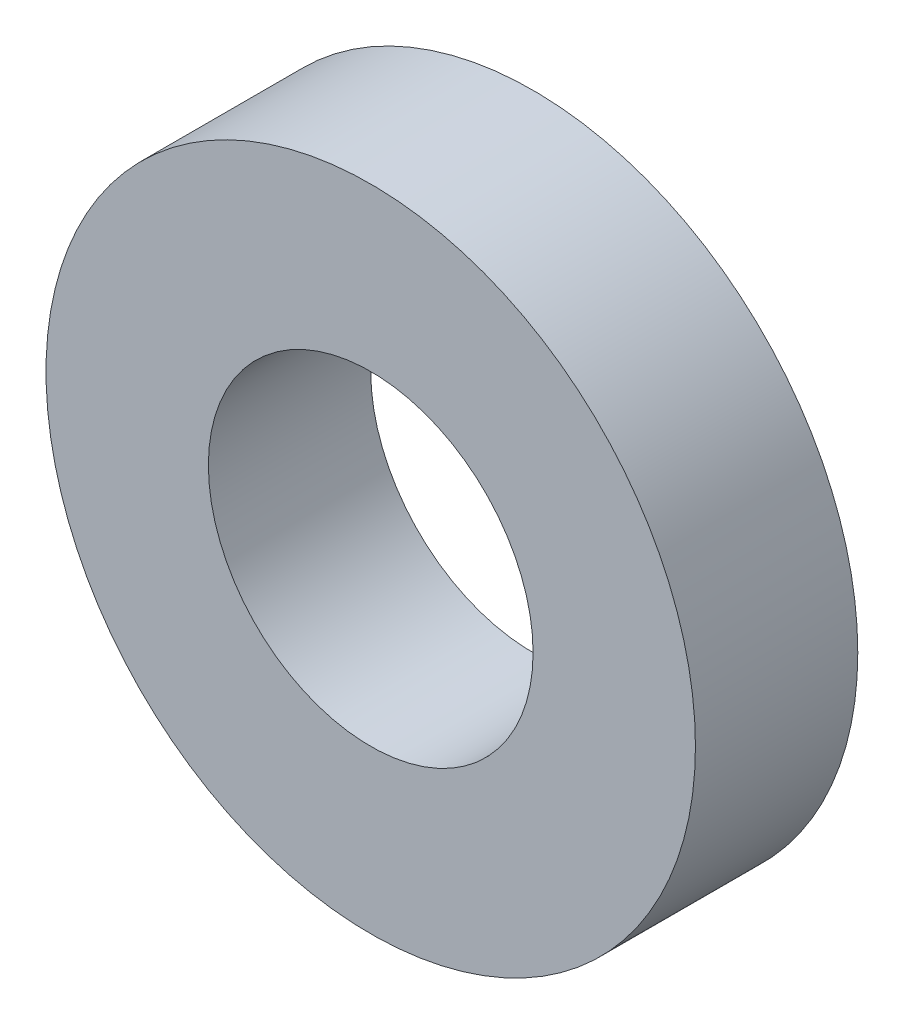
SolidWorks part; units mm, degrees
material "AISI 321 Annealed Stainless Steel (SS)"
ref_plane "Front (1)" through (0, 0, 0) normal (0, 0, 1) x (1, 0, 0)
ref_plane "Top (2)" through (0, 0, 0) normal (0, 1, 0) x (1, 0, 0)
ref_plane "Right (3)" through (0, 0, 0) normal (1, 0, 0) x (0, 0, -1)
ref_axis "X Axis" through (13.5064, 0, 0) along (-1, 0, 0)
ref_axis "Y Axis" through (0, 12.3593, 0) along (0, -1, 0)
ref_axis "Z Axis" through (0, 0, 14.1119) along (0, 0, -1)
sketch "Sketch2" plane through (0, 0, 0) normal (0, 0, 1) x (1, 0, 0)
  circle A0 centre (0, 0) radius 4
  circle A1 centre (0, 0) radius 8
  dimension "D1" = 8
  dimension "D2" = 16
extrude "Boss-Extrude1" add sketch "Sketch2" along normal mid plane 4
